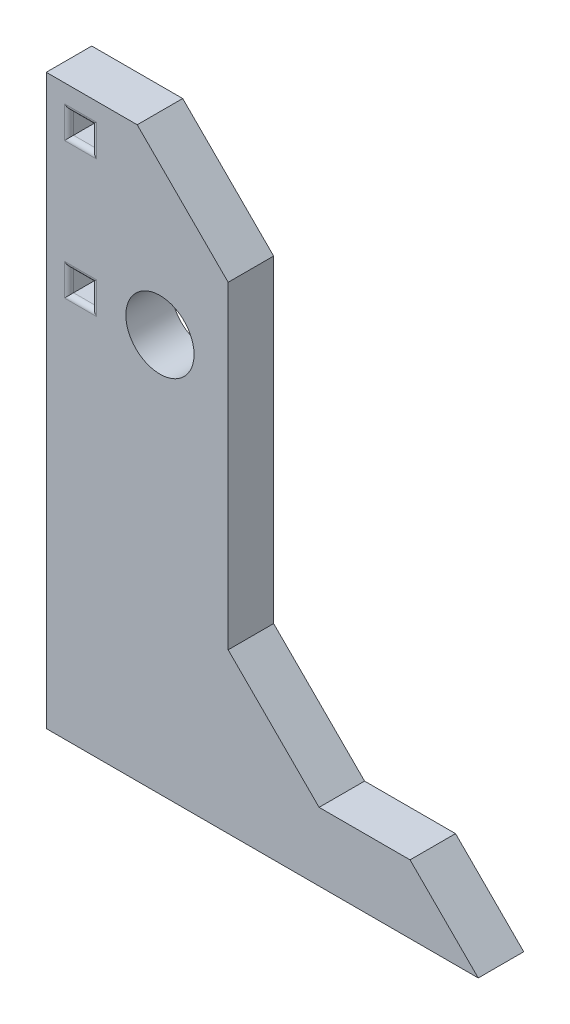
SolidWorks part; units mm, degrees
ref_plane "Front Plane" through (0, 0, 0) normal (0, 0, 1) x (1, 0, 0)
ref_plane "Top Plane" through (0, 0, 0) normal (0, 1, 0) x (1, 0, 0)
ref_plane "Right Plane" through (0, 0, 0) normal (1, 0, 0) x (0, 0, -1)
sketch "Sketch3" plane through (0, 0, 0) normal (0, 0, 1) x (1, 0, 0)
  line L4 (-80, 25) -> (-80, -26.9937)
  line L7 (120, -175) -> (-80, -175)
  line L8 (-80, -175) -> (-80, 75)
  line L9 (-80, 75) -> (0, 75)
  line L10 (0, 75) -> (0, -175)
  line L11 (120, -145) -> (120, -175)
  line L14 (120, -175) -> (53.4387, -175)
  line L16 (-80, -145) -> (120, -145)
  line L17 (-80, -145) -> (-80, -175)
  line L18 (-80, -175) -> (120, -175)
  line L19 (120, -145) -> (120, -175)
  arc A0 (0, -175) -> (-80, -175) centre (-40, -175) cw
  circle A1 centre (-30, 0) radius 15
  point P0 (-30, 0)
  point P2 (0, 0)
  point P11 (20, -175)
  point P17 (0, 0)
  point P19 (-80, -26.9937)
  point P25 (0, 0)
  dimension "D4" = 30
  dimension "D6" = 75
  dimension "D2" = 250
  dimension "D3" = 75
  dimension "D5" = 80
  dimension "D7" = 200
  dimension "D8" = 30
  dimension "D10" = 30
extrude "Boss-Extrude2" add sketch "Sketch3" along normal blind 20
sketch "Sketch4" plane through (0, 0, 20) normal (0, 0, 1) x (1, 0, 0)
  line L0 (-80, -175) -> (-80, 75) construction
  line L1 (-70, 65) -> (-60, 65)
  line L2 (-70, 65) -> (-70, 55)
  line L3 (-70, 55) -> (-60, 55)
  line L4 (-60, 65) -> (-60, 55)
  line L5 (-70, 5) -> (-60, 5)
  line L6 (-70, 5) -> (-70, -5)
  line L7 (-70, -5) -> (-60, -5)
  line L8 (-60, 5) -> (-60, -5)
  line L9 (-80, 75) -> (0, 75) construction
  point P12 (-70, 60)
  dimension "D1" = 10
  dimension "D2" = 10
  dimension "D3" = 10
  dimension "D4" = 10
  dimension "D5" = 10
  dimension "D6" = 10
  dimension "D7" = 10
  dimension "D8" = 50
extrude "Cut-Extrude1" cut sketch "Sketch4" against normal blind 20
chamfer "Chamfer1" distance 40 angle 45 3 edges at (120, -145, 10) (0, 75, 10) (0, -145, 10)
fillet "Fillet1" radius 2 16 edges at (-70, 60, 20) (-65, 65, 20) (-60, 60, 20) (-65, 55, 20) (-70, 0, 20) (-65, -5, 20) (-65, 5, 20) (-60, 0, 20) (-70, 60, 0) (-65, 65, 0) (-60, 60, 0) (-65, 55, 0) (-70, 0, 0) (-60, 0, 0) (-65, 5, 0) (-65, -5, 0)
